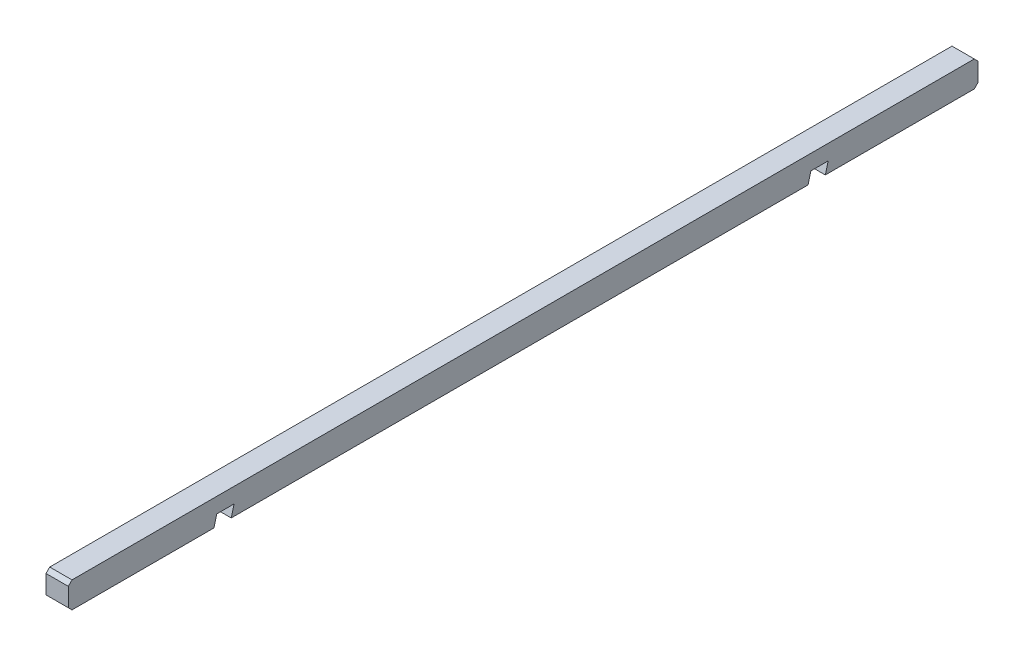
SolidWorks part; units mm, degrees
ref_plane "Front" through (0, 0, 0) normal (0, 0, 1) x (1, 0, 0)
ref_plane "Top" through (0, 0, 0) normal (0, 1, 0) x (1, 0, 0)
ref_plane "Right" through (0, 0, 0) normal (1, 0, 0) x (0, 0, -1)
sketch "Esquisse1" plane through (0, 0, 0) normal (0, 0, 1) x (1, 0, 0)
  line L1 (0, 0) -> (60, 0)
  line L2 (0, 0) -> (0, 70)
  line L3 (0, 70) -> (60, 70)
  line L4 (60, 0) -> (60, 70)
  dimension "D1" = 60
  dimension "D2" = 70
extrude "Boss.-Extru.1" add sketch "Esquisse1" along normal blind 2450
sketch "Esquisse2" plane through (0, 0, 0) normal (-1, 0, 0) x (0, 0, 1)
  line L0 (2057.7646, 0) -> (2050, 28.9778)
  line L1 (2450, 0) -> (0, 0) construction
  line L2 (2050, 28.9778) -> (2003.4126, 28.9778)
  line L3 (2003.4126, 28.9778) -> (2011.1771, 0)
  line L4 (2011.1771, 0) -> (2057.7646, 0)
  line L6 (2450, 70) -> (2450, 0) construction
  line L7 (457.7646, 0) -> (450, 28.9778)
  line L8 (450, 28.9778) -> (403.4126, 28.9778)
  line L9 (403.4126, 28.9778) -> (411.1771, 0)
  line L10 (411.1771, 0) -> (457.7646, 0)
  dimension "D1" = 75
  dimension "D2" = 30
  dimension "D3" = 45
  dimension "D4" = 400
  dimension "D6" = 1600
  dimension "D5" = 2
extrude "Enlèv. mat.-Extru.1" cut sketch "Esquisse2" against normal up to vertex (60 mm away) up to point (60, 70, 2450)
sketch "Esquisse3" plane through (0, 0, 0) normal (-1, 0, 0) x (0, 0, 1)
  line L0 (2450, 70) -> (3311.547, -1422.2432)
  line L1 (3311.547, -1422.2432) -> (3224.9445, -1472.2432)
  line L2 (3224.9445, -1472.2432) -> (2374.9445, 0)
  line L3 (2450, 0) -> (2057.7646, 0) construction
  line L6 (2374.9445, 0) -> (2450, 0)
  line L7 (2450, 70) -> (2450, 0) construction
  line L8 (2450, 0) -> (2450, 70)
  line L9 (2450, 70) -> (0, 70) construction
  dimension "D1" = 120
  dimension "D2" = 100
  dimension "D3" = 1700
chamfer "Chanfrein1" distance 10 angle 45 4 edges at (30, 70, 2450) (30, 0, 2450) (30, 0, 0) (30, 70, 0)
